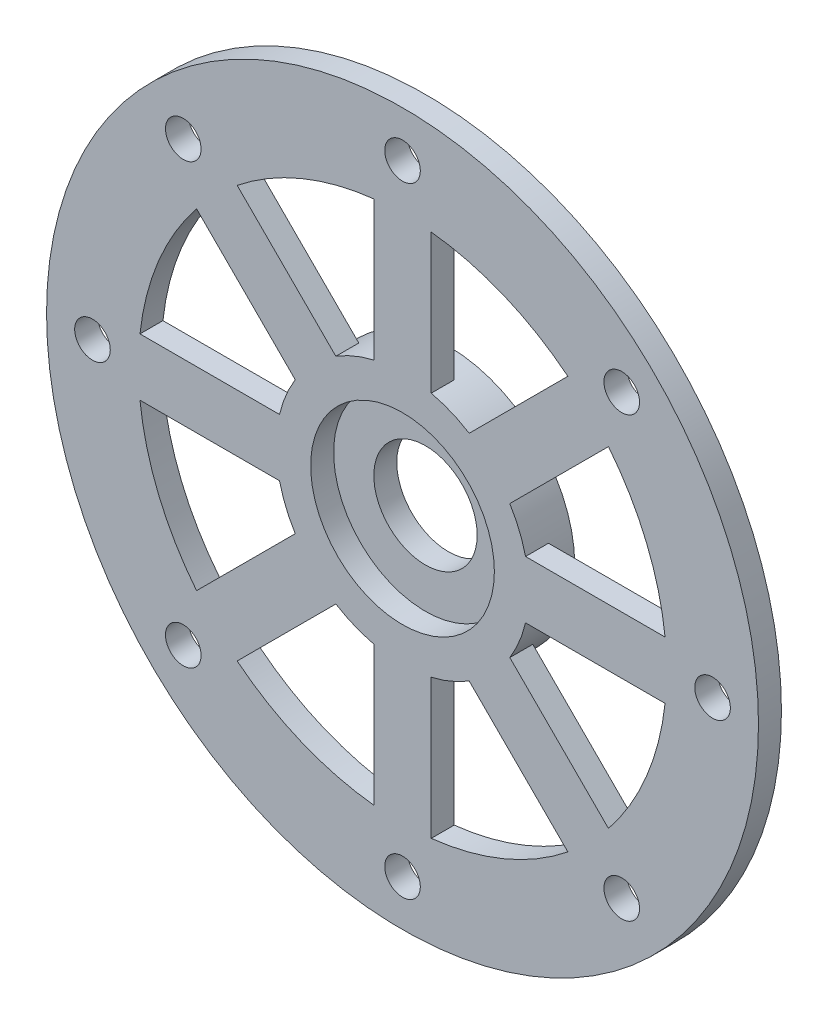
SolidWorks part; units mm, degrees
ref_plane "Front Plane" through (0, 0, 0) normal (0, 0, 1) x (1, 0, 0)
ref_plane "Top Plane" through (0, 0, 0) normal (0, 1, 0) x (1, 0, 0)
ref_plane "Right Plane" through (0, 0, 0) normal (1, 0, 0) x (0, 0, -1)
sketch "Sketch1" plane through (0, 0, 0) normal (0, 0, 1) x (1, 0, 0)
  line L0 (0, 0) -> (-27, 0) construction
  line L1 (-11, -2.5) -> (-11, 2.5) construction
  line L2 (-10.7121, 2.5) -> (-22.8637, 2.5)
  line L3 (-10.7121, -2.5) -> (-22.8637, -2.5)
  line L4 (-5.8069, 9.3424) -> (-14.3993, 17.9349)
  line L5 (-9.3424, 5.8069) -> (-17.9349, 14.3993)
  line L6 (2.5, 10.7121) -> (2.5, 22.8637)
  line L7 (-2.5, 10.7121) -> (-2.5, 22.8637)
  line L8 (9.3424, 5.8069) -> (17.9349, 14.3993)
  line L9 (5.8069, 9.3424) -> (14.3993, 17.9349)
  line L10 (10.7121, -2.5) -> (22.8637, -2.5)
  line L11 (10.7121, 2.5) -> (22.8637, 2.5)
  line L12 (5.8069, -9.3424) -> (14.3993, -17.9349)
  line L13 (9.3424, -5.8069) -> (17.9349, -14.3993)
  line L14 (-2.5, -10.7121) -> (-2.5, -22.8637)
  line L15 (2.5, -10.7121) -> (2.5, -22.8637)
  line L16 (-9.3424, -5.8069) -> (-17.9349, -14.3993)
  line L17 (-5.8069, -9.3424) -> (-14.3993, -17.9349)
  circle A0 centre (0, 0) radius 31
  circle A1 centre (-27, 0) radius 1.55
  circle A2 centre (-19.0919, 19.0919) radius 1.55
  circle A3 centre (0, 27) radius 1.55
  circle A4 centre (19.0919, 19.0919) radius 1.55
  circle A5 centre (27, 0) radius 1.55
  circle A6 centre (19.0919, -19.0919) radius 1.55
  circle A7 centre (0, -27) radius 1.55
  circle A8 centre (-19.0919, -19.0919) radius 1.55
  arc A9 (-22.8637, -2.5) -> (-17.9349, -14.3993) centre (0, 0) ccw
  arc A10 (-10.7121, -2.5) -> (-9.3424, -5.8069) centre (0, 0) ccw
  arc A11 (-17.9349, 14.3993) -> (-22.8637, 2.5) centre (0, 0) ccw
  arc A12 (-9.3424, 5.8069) -> (-10.7121, 2.5) centre (0, 0) ccw
  arc A13 (-2.5, 10.7121) -> (-5.8069, 9.3424) centre (0, 0) ccw
  arc A14 (-2.5, 22.8637) -> (-14.3993, 17.9349) centre (0, 0) ccw
  arc A15 (14.3993, 17.9349) -> (2.5, 22.8637) centre (0, 0) ccw
  arc A16 (5.8069, 9.3424) -> (2.5, 10.7121) centre (0, 0) ccw
  arc A17 (10.7121, 2.5) -> (9.3424, 5.8069) centre (0, 0) ccw
  arc A18 (9.3424, -5.8069) -> (10.7121, -2.5) centre (0, 0) ccw
  arc A19 (2.5, -10.7121) -> (5.8069, -9.3424) centre (0, 0) ccw
  arc A20 (-5.8069, -9.3424) -> (-2.5, -10.7121) centre (0, 0) ccw
  arc A21 (22.8637, 2.5) -> (17.9349, 14.3993) centre (0, 0) ccw
  arc A22 (17.9349, -14.3993) -> (22.8637, -2.5) centre (0, 0) ccw
  arc A23 (2.5, -22.8637) -> (14.3993, -17.9349) centre (0, 0) ccw
  arc A24 (-14.3993, -17.9349) -> (-2.5, -22.8637) centre (0, 0) ccw
  point P21 (0, 0)
  point P25 (-11, 0)
  point P57 (0, 0)
  dimension "D1" = 8
  dimension "D2" = 8
extrude "Boss-Extrude1" add sketch "Sketch1" along normal blind 2
sketch "Sketch3" plane through (0, 0, 0) normal (0, 0, -1) x (-1, 0, 0)
  circle A0 centre (0, 0) radius 11
extrude "Boss-Extrude2" add sketch "Sketch3" along normal blind 2
sketch "Sketch4" plane through (0, 0, 2) normal (0, 0, 1) x (1, 0, 0)
  circle A0 centre (0, 0) radius 4.5
extrude "Cut-Extrude2" cut sketch "Sketch4" against normal up to surface (4 mm away) up to face at (-11, 0, -2)
sketch "Sketch2" plane through (0, 0, 2) normal (0, 0, 1) x (1, 0, 0)
  circle A0 centre (0, 0) radius 8
extrude "Cut-Extrude1" cut sketch "Sketch2" against normal blind 2
